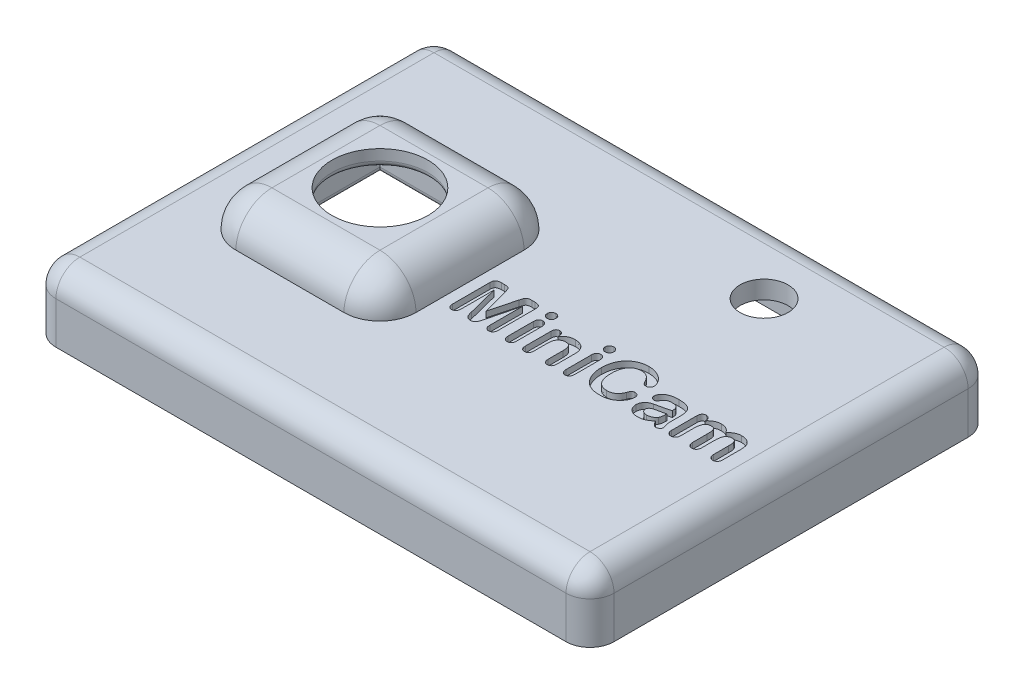
SolidWorks part; units mm, degrees
ref_plane "Front Plane" through (0, 0, 0) normal (0, 0, 1) x (1, 0, 0)
ref_plane "Top Plane" through (0, 0, 0) normal (0, 1, 0) x (1, 0, 0)
ref_plane "Right Plane" through (0, 0, 0) normal (1, 0, 0) x (0, 0, -1)
sketch "Sketch1" plane through (0, 0, 0) normal (0, 1, 0) x (1, 0, 0)
  line L1 (0, 0) -> (-46.5, 0)
  line L2 (0, 0) -> (0, 33.5)
  line L3 (0, 33.5) -> (-46.5, 33.5)
  line L4 (-46.5, 0) -> (-46.5, 33.5)
  dimension "D1" = 46.5
  dimension "D2" = 33.5
extrude "Boss-Extrude2" add sketch "Sketch1" along normal blind 1.5
sketch "Sketch2" plane through (0, 1.5, 0) normal (0, 1, 0) x (1, 0, 0)
  line L5 (-41.5, 24) -> (-26.5, 24)
  line L6 (-41.5, 24) -> (-41.5, 9)
  line L7 (-41.5, 9) -> (-26.5, 9)
  line L8 (-26.5, 24) -> (-26.5, 9)
  line L9 (-41.5, 24) -> (-26.5, 9) construction
  line L10 (-41.5, 9) -> (-26.5, 24) construction
  point P4 (-34, 16.5)
  dimension "D1" = 34
  dimension "D2" = 16.5
  dimension "D3" = 15
  dimension "D4" = 15
extrude "Boss-Extrude3" add sketch "Sketch2" along normal blind 3
sketch "Sketch3" plane through (0, 0, 0) normal (0, -1, 0) x (-1, 0, 0)
  line L0 (45.5, 1) -> (45.5, 32.5)
  line L1 (46.5, 0) -> (0, 0)
  line L2 (46.5, 0) -> (46.5, 33.5)
  line L3 (46.5, 33.5) -> (0, 33.5)
  line L4 (0, 0) -> (0, 33.5)
  line L5 (45.5, 32.5) -> (1, 32.5)
  line L6 (1, 1) -> (1, 32.5)
  line L7 (45.5, 1) -> (1, 1)
  dimension "D1" = 1
extrude "Boss-Extrude4" add sketch "Sketch3" along normal blind 4
sketch "Sketch4" plane through (0, -4, 0) normal (0, -1, 0) x (-1, 0, 0)
  line L1 (48.2558, 9.5) -> (43.2448, 9.5)
  line L2 (48.2558, 9.5) -> (48.2558, 22.5)
  line L3 (48.2558, 22.5) -> (43.2448, 22.5)
  line L4 (43.2448, 9.5) -> (43.2448, 22.5)
  dimension "D1" = 13
  dimension "D2" = 22.5
extrude "Cut-Extrude1" cut sketch "Sketch4" against normal blind 3
fillet "Fillet2" radius 2 8 edges at (0, 1.5, -16.75) (-23.25, 1.5, 0) (-23.25, 1.5, -33.5) (-46.5, 1.5, -16.75) (-46.5, -1.25, -33.5) (0, -1.25, -33.5) (0, -1.25, 0) (-46.5, -1.25, 0)
sketch "Sketch6" plane through (0, 4.5, 0) normal (0, 1, 0) x (1, 0, 0)
  circle A0 centre (-34, 16.5) radius 4
  dimension "D3" = 8
  dimension "D1" = 34
  dimension "D2" = 16.5
extrude "Cut-Extrude2" cut sketch "Sketch6" against normal blind 13
fillet "Fillet3" radius 3 4 edges at (-34, 4.5, -24) (-26.5, 4.5, -16.5) (-34, 4.5, -9) (-41.5, 4.5, -16.5)
sketch "Sketch7" plane through (0, 0, 0) normal (0, -1, 0) x (-1, 0, 0)
  line L1 (39.5, 22) -> (28.5, 22)
  line L2 (39.5, 22) -> (39.5, 11)
  line L3 (39.5, 11) -> (28.5, 11)
  line L4 (28.5, 22) -> (28.5, 11)
  line L5 (39.5, 22) -> (28.5, 11) construction
  line L6 (39.5, 11) -> (28.5, 22) construction
  point P0 (34, 16.5)
  dimension "D1" = 11
  dimension "D2" = 11
extrude "Cut-Extrude3" cut sketch "Sketch7" against normal blind 3.1
sketch "Sketch8" plane through (0, 1.5, 0) normal (0, 1, 0) x (1, 0, 0)
  text T0 "MiniCam" font "Arial Rounded MT Bold" height in points 16
extrude "Cut-Extrude4" cut sketch "Sketch8" against normal blind 0.5
sketch "Sketch9" plane through (0, 1.5, 0) normal (0, 1, 0) x (1, 0, 0)
  circle A0 centre (-13, 27.5) radius 2
  dimension "D3" = 4
  dimension "D1" = 13
  dimension "D2" = 27.5
extrude "Cut-Extrude5" cut sketch "Sketch9" against normal blind 10
fillet "Fillet4" radius 0.5 5 edges at (-39.5, 0, -16.5) (-34, 0, -11) (-28.5, 0, -16.5) (-34, 0, -22) (-34, 3.1, -12.5)
